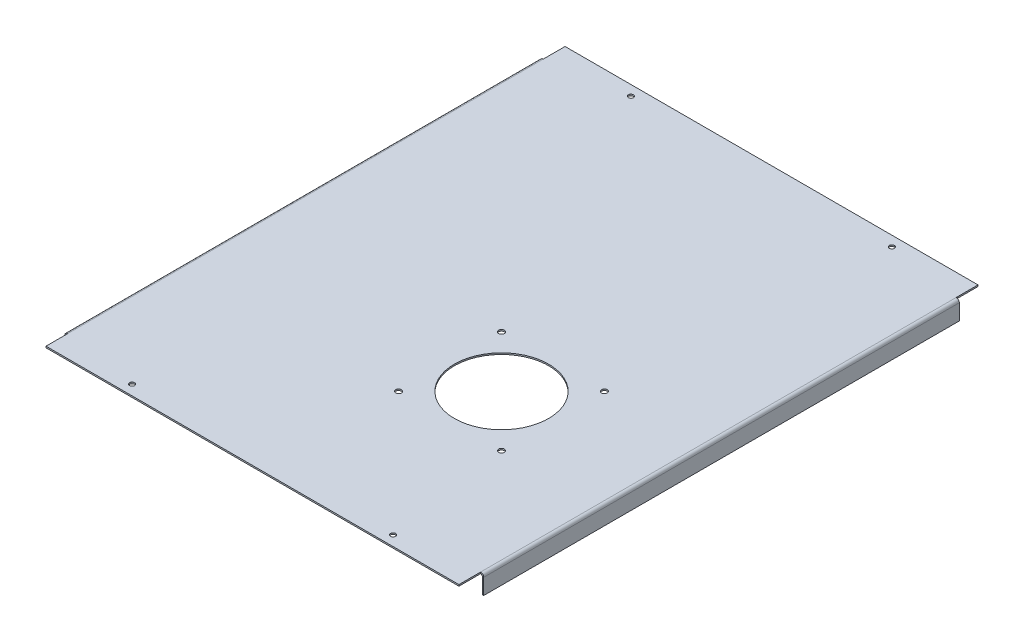
SolidWorks part; units mm, degrees
note: The reader was unsure of these and kept them because the rebuilt part matched: flange length of "Ребро-кромка1".
ref_plane "Спереди" through (0, 0, 0) normal (0, 0, 1) x (1, 0, 0)
ref_plane "Сверху" through (0, 0, 0) normal (0, 1, 0) x (1, 0, 0)
ref_plane "Справа" through (0, 0, 0) normal (1, 0, 0) x (0, 0, -1)
sketch "Эскиз1" plane through (0, 0, 0) normal (0, 1, 0) x (1, 0, 0)
  line L1 (-35.4278, 46.7063) -> (251.5722, 46.7063)
  line L2 (-35.4278, 46.7063) -> (-35.4278, -311.2937)
  line L3 (-35.4278, -311.2937) -> (251.5722, -311.2937)
  line L4 (251.5722, 46.7063) -> (251.5722, -311.2937)
  dimension "D1" = 287
  dimension "D2" = 358
sheet metal parameters "Листовой металл1" thickness 1 parameters "D1"=1.1
base flange "Базовая кромка1" sketch "Эскиз1" thickness 1 reverse thickness direction no parameters "D1"=1.1
edge flange "Ребро-кромка1" sketch "Эскиз8" flange profiles "Эскиз8", "Эскиз9" flange angle 90 flange length 12 flange position material outside bend radius 1.1 thickness 1 relief rectangular parameters "D6"=10, "D8"=1
sketch "Эскиз8" plane through (251.5722, -1, 0) normal (1, 0, 0) x (0, 0, 1)
  line L0 (311.2937, 0) -> (-46.7063, 0) construction
  line L1 (311.2937, 0) -> (-46.7063, 0)
  line L2 (-46.7063, 0) -> (-46.7063, 12)
  line L3 (-46.7063, 12) -> (311.2937, 12)
  line L4 (311.2937, 12) -> (311.2937, 0)
sketch "Эскиз9" plane through (-35.4278, -1, 0) normal (-1, 0, 0) x (0, 0, -1)
  line L0 (46.7063, 0) -> (-311.2937, 0) construction
  line L1 (46.7063, 0) -> (-311.2937, 0)
  line L2 (-311.2937, 0) -> (-311.2937, 12)
  line L3 (-311.2937, 12) -> (46.7063, 12)
  line L4 (46.7063, 12) -> (46.7063, 0)
bend "EdgeBend1" bend radius 1.1 bend angle 90 parameters "D5"=1
bend "EdgeBend2" bend radius 1.1 bend angle 90 parameters "D5"=2
sketch "Эскиз10" plane through (252.5722, 0, 0) normal (1, 0, 0) x (0, 0, -1)
  line L1 (46.7063, -13) -> (31.7063, -13)
  line L2 (46.7063, -13) -> (46.7063, 2)
  line L3 (46.7063, 2) -> (31.7063, 2)
  line L4 (31.7063, -13) -> (31.7063, 2)
  dimension "D1" = 15
  dimension "D2" = 15
extrude "Вырез-Вытянуть2" cut sketch "Эскиз10" against normal blind 2.1 normal cut yes
sketch "Эскиз11" plane through (252.5722, 0, 0) normal (1, 0, 0) x (0, 0, -1)
  line L1 (-311.2937, -13) -> (-296.2937, -13)
  line L2 (-311.2937, -13) -> (-311.2937, 1.6973)
  line L3 (-311.2937, 1.6973) -> (-296.2937, 1.6973)
  line L4 (-296.2937, -13) -> (-296.2937, 1.6973)
  dimension "D1" = 15
extrude "Вырез-Вытянуть3" cut sketch "Эскиз11" against normal blind 2.1 normal cut yes
sketch "Эскиз12" plane through (-36.4278, 0, 0) normal (-1, 0, 0) x (0, 0, 1)
  line L1 (311.2937, -13) -> (296.2937, -13)
  line L2 (311.2937, -13) -> (311.2937, 1.8306)
  line L3 (311.2937, 1.8306) -> (296.2937, 1.8306)
  line L4 (296.2937, -13) -> (296.2937, 1.8306)
  dimension "D1" = 15
extrude "Вырез-Вытянуть4" cut sketch "Эскиз12" against normal blind 2.1 normal cut yes
sketch "Эскиз13" plane through (-36.4278, 0, 0) normal (-1, 0, 0) x (0, 0, 1)
  line L1 (-46.7063, -13) -> (-31.7063, -13)
  line L2 (-46.7063, -13) -> (-46.7063, 3.6108)
  line L3 (-46.7063, 3.6108) -> (-31.7063, 3.6108)
  line L4 (-31.7063, -13) -> (-31.7063, 3.6108)
  dimension "D1" = 15
extrude "Вырез-Вытянуть5" cut sketch "Эскиз13" against normal blind 2.1 normal cut yes
sketch "Эскиз14" plane through (0, 0, 0) normal (0, 1, 0) x (1, 0, 0)
  line L0 (-34.3278, 39.7063) -> (250.4722, 39.7063) construction
  line L1 (-34.3278, 46.7063) -> (-34.3278, 31.7063) construction
  line L2 (250.4722, 31.7063) -> (250.4722, 46.7063) construction
  line L3 (250.4722, 46.7063) -> (-34.3278, 46.7063) construction
  line L4 (-34.3278, -304.2937) -> (250.4722, -304.2937) construction
  line L5 (-34.3278, -296.2937) -> (-34.3278, -311.2937) construction
  line L6 (250.4722, -311.2937) -> (250.4722, -296.2937) construction
  line L7 (-34.3278, -311.2937) -> (250.4722, -311.2937) construction
  line L8 (108.0722, 46.7063) -> (108.0722, -311.2937) construction
  circle A0 centre (18.0722, -304.2937) radius 1.75
  circle A1 centre (198.0722, -304.2937) radius 1.75
  circle A2 centre (18.0722, 39.7063) radius 1.75
  circle A3 centre (198.0722, 39.7063) radius 1.75
  dimension "D3" = 3.5
  dimension "D4" = 3.5
  dimension "D5" = 3.5
  dimension "D6" = 3.5
  dimension "D8" = 90
  dimension "D10" = 90
  dimension "D1" = 7
  dimension "D2" = 7
  dimension "D7" = 90
  dimension "D9" = 90
extrude "Вырез-Вытянуть6" cut sketch "Эскиз14" against normal blind 10 normal cut yes
sketch "Эскиз15" plane through (0, 0, 0) normal (0, 1, 0) x (1, 0, 0)
  circle A0 centre (149.7104, -181.1678) radius 32.5
  dimension "D1" = 65
extrude "Вырез-Вытянуть7" cut sketch "Эскиз15" against normal blind 10 normal cut yes
sketch "Эскиз16" plane through (0, -1, 0) normal (0, -1, 0) x (1, 0, 0)
  circle A0 centre (114.2102, 216.6676) radius 2
  circle A1 centre (185.2102, 216.668) radius 2
  circle A2 centre (114.2106, 145.6676) radius 2
  circle A3 centre (185.2106, 145.668) radius 2
  dimension "D1" = 4
  dimension "D2" = 4
  dimension "D3" = 4
  dimension "D4" = 4
extrude "Вырез-Вытянуть8" cut sketch "Эскиз16" against normal blind 10 normal cut yes
flat pattern "Развертка1" [suppressed]
sketch "Сгиб-Линии1" plane through (0, 0, 0) normal (0, 1, 0) x (1, 0, 0)
sketch3d "Граничная рамка1" [suppressed]
  line L0 (35.4278, 46.7063, 0) -> (35.4278, -277.2937, 0) construction
  line L1 (-253.5722, 46.7063, 0) -> (-253.5722, -277.2937, 0) construction
  line L2 (35.4278, 46.7063, 0) -> (-253.5722, 46.7063, 0) construction
  line L3 (35.4278, -277.2937, 0) -> (-253.5722, -277.2937, 0) construction
bend of the flat pattern "Плоское состояние-<EdgeBend1>1"
bend of the flat pattern "Плоское состояние-<EdgeBend2>1"
